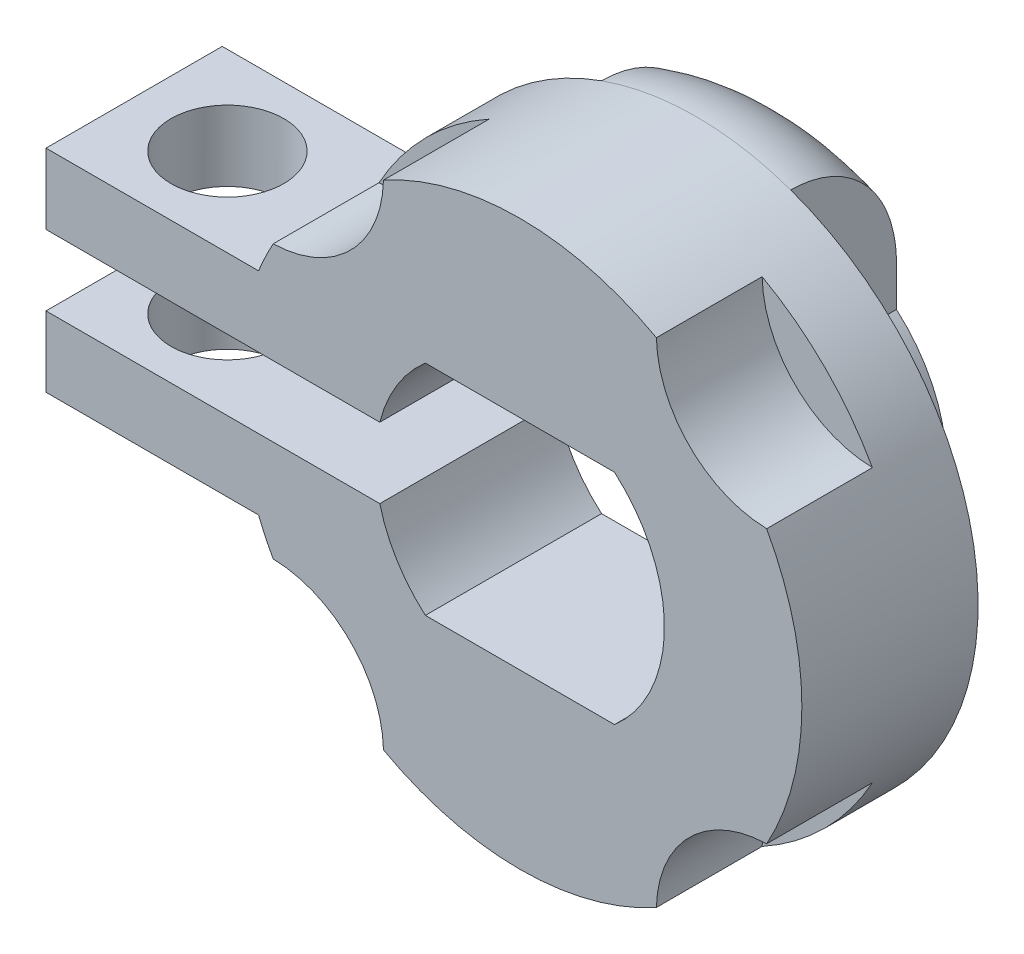
SolidWorks part; units mm, degrees
ref_plane "前视基准面" through (0, 0, 0) normal (0, 0, 1) x (1, 0, 0)
ref_plane "上视基准面" through (0, 0, 0) normal (0, 1, 0) x (1, 0, 0)
ref_plane "右视基准面" through (0, 0, 0) normal (1, 0, 0) x (0, 0, -1)
sketch "草图1" plane through (0, 0, 0) normal (0, 0, 1) x (1, 0, 0)
  circle A1 centre (0, 0) radius 14
  circle A3 centre (-7.0711, 7.0711) radius 1.5
  circle A4 centre (7.0711, 7.0711) radius 1.5
  circle A5 centre (-7.0711, -7.0711) radius 1.5
  circle A6 centre (7.0711, -7.0711) radius 1.5
extrude "凸台-拉伸1" add sketch "草图1" along normal blind 2
sketch "草图2" plane through (0, 0, 0) normal (0, 0, -1) x (-1, 0, 0)
  line L9 (-2.6885, -3.1) -> (2.6885, -3.1)
  line L10 (-2.6833, 3.1) -> (2.6833, 3.1)
  line L14 (-2.6833, -3.1) -> (2.6833, -3.1)
  arc A1 (-2.6833, 3.1) -> (-2.6833, -3.1) centre (0, 0) ccw
  arc A2 (2.6833, 3.1) -> (2.6833, -3.1) centre (0, 0) cw
  point P2 (0, 3.1)
  point P4 (0, -3.1)
extrude "切除-拉伸1" cut sketch "草图2" against normal through all contours A2 L10 A1 L9 region at (0, 0, 0)
sketch "草图3" plane through (0, 0, 0) normal (0, 0, -1) x (-1, 0, 0)
  line L0 (0, 3.1) -> (3.7, 3.1)
  line L1 (-2.6833, 3.1) -> (2.6833, 3.1) construction
  line L2 (3.7, 3.1) -> (3.7, 7.1)
  line L3 (0, 3.1) -> (-3.7, 3.1)
  line L4 (-3.7, 3.1) -> (-3.7, 7.1)
  line L5 (-3.7, 7.1) -> (3.7, 7.1)
extrude "凸台-拉伸4" add sketch "草图3" along normal blind 2.5
sketch "草图6" plane through (0, 0, -2.5) normal (0, 0, -1) x (-1, 0, 0)
  line L0 (-2.6833, -3.1) -> (2.6833, -3.1) construction
  line L1 (-2.6833, -3.1) -> (2.6833, -3.1)
  line L2 (-2.6833, 3.1) -> (2.6833, 3.1)
  arc A0 (-2.6833, 3.1) -> (-2.6833, -3.1) centre (0, 0) ccw
  arc A1 (2.6833, 3.1) -> (2.6833, -3.1) centre (0, 0) cw
  circle A2 centre (0, 0) radius 8
extrude "凸台-拉伸5" add sketch "草图6" along normal blind 5
sketch "草图7" plane through (0, 0, -7.5) normal (0, 0, -1) x (-1, 0, 0)
  line L0 (-2.6833, 3.1) -> (-2.6833, 7.5366)
  line L1 (2.6833, 3.1) -> (2.6833, 7.5366)
  line L2 (-2.6833, 3.1) -> (2.6833, 3.1)
  arc A0 (-2.6833, 7.5366) -> (2.6833, 7.5366) centre (0, 0) cw
  circle A1 centre (0, 0) radius 8 construction
extrude "凸台-拉伸6" add sketch "草图7" along normal blind 1
sketch "草图8" plane through (0, 0, -7.5) normal (0, 0, -1) x (-1, 0, 0)
  line L2 (5.4474, 3) -> (5.4474, 1)
  line L5 (5.4474, 1) -> (13.4474, 1)
  line L6 (13.4474, 1) -> (13.4474, 3)
  line L7 (13.4474, 3) -> (5.4474, 3)
  line L10 (5.4474, -3) -> (13.4474, -3)
  line L11 (13.4474, -3) -> (13.4474, -1)
  line L12 (13.4474, -1) -> (5.4474, -1)
  line L14 (5.4474, -1) -> (5.4474, -3)
extrude "凸台-拉伸7" add sketch "草图8" against normal blind 5
sketch "草图9" plane through (0, 3, 0) normal (0, 1, 0) x (1, 0, 0)
  circle A0 centre (-10.8, 5) radius 1.6
extrude "切除-拉伸3" cut sketch "草图9" against normal through all contours A0
sketch "草图10" plane through (0, 0, -8.5) normal (0, 0, -1) x (-1, 0, 0)
  line L9 (-2.6833, 7.5366) -> (-2.6833, 3.1)
  line L10 (2.6833, 7.5366) -> (2.6833, 3.1)
  arc A2 (-2.6833, 3.1) -> (2.6833, 3.1) centre (0, 0) ccw
  arc A3 (-2.6833, 7.5366) -> (2.6833, 7.5366) centre (0, 0) cw
extrude "凸台-拉伸8" add sketch "草图10" along normal blind 2
sketch "草图11" plane through (0, 0, -7.5) normal (0, 0, -1) x (-1, 0, 0)
  line L0 (13.4474, 1) -> (1.4059, 1)
  line L1 (13.4474, -1) -> (1.4059, -1)
  line L2 (1.4059, -1) -> (1.4059, 1)
  line L3 (13.4474, 1) -> (13.4474, -1)
extrude "切除-拉伸4" cut sketch "草图11" against normal blind 5
fillet "圆角2" radius 3 1 edges at (0, 8, -10.5)
sketch "草图12" plane through (0, 0, 2) normal (0, 0, 1) x (1, 0, 0)
  circle A0 centre (0, 0) radius 14
extrude "切除-拉伸5" cut sketch "草图12" against normal blind 4.5
sketch "草图13" plane through (0, 0, -2.5) normal (0, 0, 1) x (1, 0, 0)
  line L6 (-7.0711, -7.0711) -> (7.0711, 7.0711) construction
  line L7 (-7.0711, 7.0711) -> (7.0711, -7.0711) construction
  circle A0 centre (-7.0711, 7.0711) radius 3.2
  circle A1 centre (7.0711, 7.0711) radius 3.2
  circle A2 centre (-7.0711, -7.0711) radius 3.2
  circle A3 centre (7.0711, -7.0711) radius 3.2
extrude "切除-拉伸6" cut sketch "草图13" against normal blind 3
